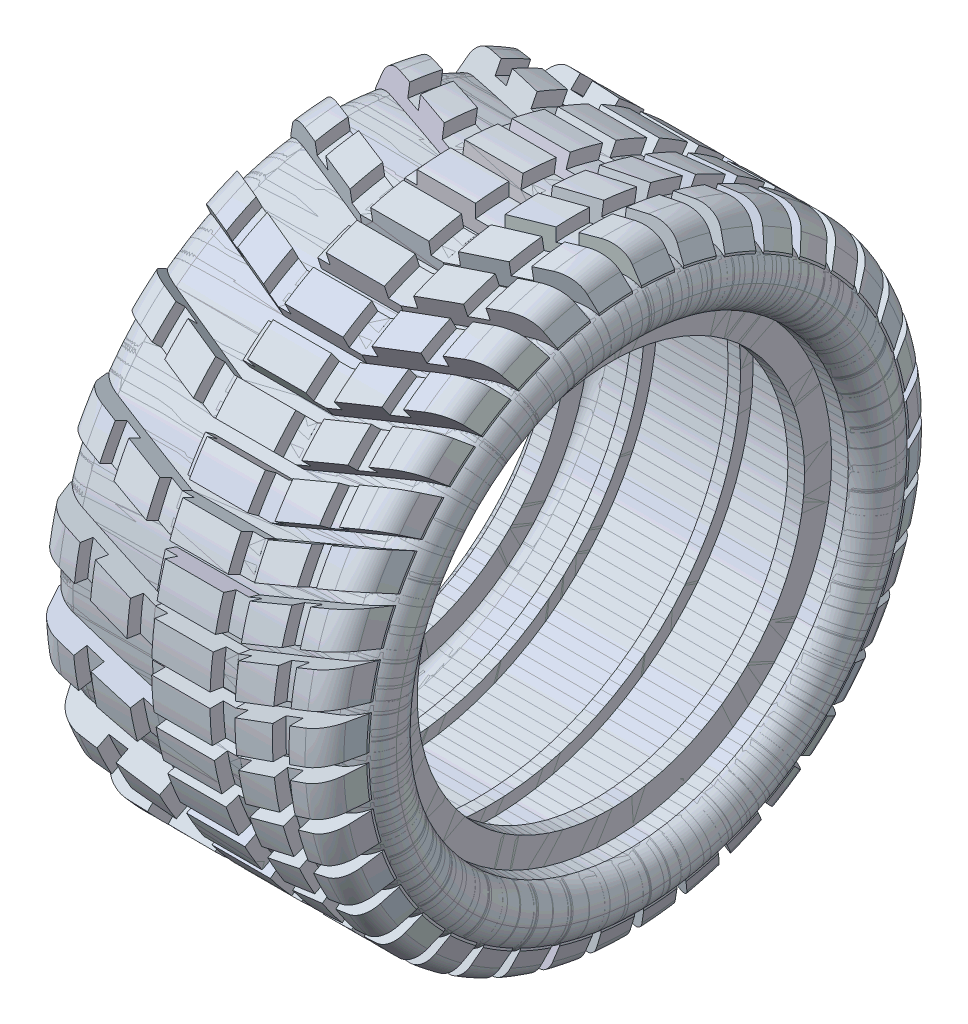
SolidWorks part; units mm, degrees
material "Rubber"
ref_plane "Front Plane" through (0, 0, 0) normal (0, 0, 1) x (1, 0, 0)
ref_plane "Top Plane" through (0, 0, 0) normal (0, 1, 0) x (1, 0, 0)
ref_plane "Right Plane" through (0, 0, 0) normal (1, 0, 0) x (0, 0, -1)
sketch "Sketch1" plane through (0, 0, 0) normal (0, 0, 1) x (1, 0, 0)
  line L0 (-30.5, 25.5) -> (-30.5, -25.5) construction
  line L1 (-30.5, 23.25) -> (-32.5, 23.25) construction
  line L2 (-32.5, -26.5) -> (-32.5, 26.5) construction
  line L3 (-32.5, 26.5) -> (-34.5, 26.5) construction
  line L4 (-30.5, 25.5) -> (-30.5, 23.25)
  line L5 (-30.5, 23.25) -> (-32.5, 23.25)
  line L6 (-32.5, 23.25) -> (-32.5, 26.5)
  line L7 (-32.5, 26.5) -> (-34.5, 26.5)
  line L8 (-17.25, 23.25) -> (-17.25, 39.4881) construction
  line L9 (-5, 23.25) -> (-29.5, 23.25) construction
  line L10 (-33.1867, 33.3757) -> (-1.3133, 33.3757)
  line L11 (-30.5, 25.5) -> (-30.5, 25.9278)
  line L12 (-32.6213, 28.0492) -> (-33.1867, 28.0492)
  line L13 (-33.1867, 31.5757) -> (-29.5, 31.5757)
  line L14 (-16.5, 30.0757) -> (-18, 30.0757)
  line L15 (-18, 30.0757) -> (-18, 31.5757)
  line L16 (-29.5, 31.5757) -> (-29.5, 30.0757)
  line L17 (-29.5, 30.0757) -> (-28, 30.0757)
  line L18 (-28, 30.0757) -> (-28, 31.5757)
  line L19 (-28, 31.5757) -> (-18, 31.5757)
  line L20 (-30.5, 25.9278) -> (-32.6213, 28.0492)
  line L21 (-4, 25.9278) -> (-1.8787, 28.0492)
  line L22 (-6.5, 31.5757) -> (-16.5, 31.5757)
  line L23 (-6.5, 30.0757) -> (-6.5, 31.5757)
  line L24 (-5, 30.0757) -> (-6.5, 30.0757)
  line L25 (-5, 31.5757) -> (-5, 30.0757)
  line L26 (-16.5, 30.0757) -> (-16.5, 31.5757)
  line L27 (-1.3133, 31.5757) -> (-5, 31.5757)
  line L28 (-1.8787, 28.0492) -> (-1.3133, 28.0492)
  line L29 (-4, 25.5) -> (-4, 25.9278)
  line L30 (-2, 26.5) -> (0, 26.5)
  line L31 (-2, 23.25) -> (-2, 26.5)
  line L32 (-4, 23.25) -> (-2, 23.25)
  line L33 (-4, 25.5) -> (-4, 23.25)
  line L34 (0, 0) -> (-51.0167, 0) construction
  line L35 (-36.75, 29.8124) -> (-36.75, 39.4881) construction
  line L36 (2.25, 29.8124) -> (2.25, 36.5986) construction
  arc A0 (-34.5, 26.5) -> (-33.1867, 33.3757) centre (-33.1867, 29.8124) cw
  arc A1 (-33.1867, 28.0492) -> (-33.1867, 31.5757) centre (-33.1867, 29.8124) cw
  arc A2 (-1.3133, 28.0492) -> (-1.3133, 31.5757) centre (-1.3133, 29.8124) ccw
  arc A3 (0, 26.5) -> (-1.3133, 33.3757) centre (-1.3133, 29.8124) ccw
  point P38 (-17.25, 30.0757)
  point P39 (-17.25, 33.3757)
  dimension "D1" = 7
  dimension "D2" = 1.8
  dimension "D3" = 1.5
  dimension "D4" = 10
  dimension "D5" = 45
  dimension "D6" = 3
  dimension "D7" = 39
revolve "Revolve1" add sketch "Sketch1" angle 360 about L34
ref_plane "Plane1" through (0, 50, 0) normal (0, 1, 0) x (-1, 0, 0)
sketch "Sketch3" plane through (0, 50, 0) normal (0, 1, 0) x (-1, 0, 0)
  line L0 (33.1867, 0) -> (1.3133, 0) construction
  line L1 (17.25, 0.5) -> (17.25, -0.5) construction
  line L2 (22.25, -0.5) -> (12.25, -0.5) construction
  line L3 (22.25, -0.5) -> (22.25, -4.5) construction
  line L4 (22.25, -4.5) -> (12.25, -4.5) construction
  line L5 (12.25, -0.5) -> (12.25, -4.5) construction
  line L6 (22.25, 4.5) -> (12.25, 4.5)
  line L7 (22.25, 4.5) -> (22.25, 0.5)
  line L8 (22.25, 0.5) -> (12.25, 0.5)
  line L9 (12.25, 4.5) -> (12.25, 0.5) construction
  line L10 (33.1867, -33.3757) -> (33.1867, 33.3757) construction
  line L11 (-1.25, -0.4136) -> (-1.25, -4.4136)
  line L12 (1.3133, -33.3757) -> (1.3133, 33.3757) construction
  line L13 (35.75, -9.4136) -> (35.75, -5.4136) construction
  line L14 (-1.25, -0.4136) -> (12.25, 4.5)
  line L15 (12.25, 0.5) -> (-1.25, -4.4136)
  line L16 (22.25, -0.5) -> (35.75, -5.4136) construction
  line L17 (22.25, -4.5) -> (35.75, -9.4136) construction
  line L21 (35.75, -29.8124) -> (35.75, 29.8124)
  line L22 (35.75, -29.8124) -> (35.75, 29.8124) construction
  line L24 (-1.25, 29.8124) -> (-1.25, -29.8124)
  line L25 (-1.25, 29.8124) -> (-1.25, -29.8124) construction
  point P12 (17.25, 0)
  dimension "D1" = 4
  dimension "D2" = 10
  dimension "D3" = 1
  dimension "D4" = 200
  dimension "D5" = 200
  dimension "D6" = 1
  dimension "D7" = 1
extrude "Boss-Extrude1" add sketch "Sketch3" against normal up to next
ref_plane "Plane2" through (-17.25, 0, 0) normal (-1, 0, 0) x (0, 0, 1)
pattern_circular "CirPattern1" count 20 over 360 about axis through (0, 0, 0) along (1, 0, 0) of "Boss-Extrude1"
sketch "Sketch4" plane through (0, 0, 0) normal (0, 0, 1) x (1, 0, 0)
  line L0 (-35.95, 32.0622) -> (-34.95, 34.5075)
  line L1 (-22.25, 33.372) -> (-12.25, 33.372) construction
  line L2 (-32.1732, 36.372) -> (-30.25, 36.372)
  line L3 (-1.3133, 0) -> (-33.1867, 0) construction
  line L4 (-33.1867, 31.5757) -> (-33.1867, -31.5757) construction
  line L5 (-17.25, 0) -> (-17.25, 64.8866) construction
  line L6 (-1.3133, 9.8185) -> (-1.3133, 3.4806) construction
  line L7 (-35.95, 32.0622) -> (-43.929, 56.5045)
  line L8 (-43.929, 56.5045) -> (9.429, 56.5045)
  line L9 (-20.75, 36.372) -> (-20.75, 34.772)
  line L10 (-20.75, 34.772) -> (-23.75, 34.772)
  line L11 (-23.75, 34.772) -> (-23.75, 36.372)
  line L12 (-28.25, 36.372) -> (-28.25, 34.772)
  line L13 (-28.25, 34.772) -> (-30.25, 34.772)
  line L14 (-30.25, 34.772) -> (-30.25, 36.372)
  line L15 (-28.25, 36.372) -> (-23.75, 36.372)
  line L16 (-20.75, 36.372) -> (-13.75, 36.372)
  line L17 (-6.25, 36.372) -> (-10.75, 36.372)
  line L18 (-4.25, 34.772) -> (-4.25, 36.372)
  line L19 (-6.25, 34.772) -> (-4.25, 34.772)
  line L20 (-6.25, 36.372) -> (-6.25, 34.772)
  line L21 (-10.75, 34.772) -> (-10.75, 36.372)
  line L22 (-13.75, 34.772) -> (-10.75, 34.772)
  line L23 (-13.75, 36.372) -> (-13.75, 34.772)
  line L24 (1.45, 32.0622) -> (9.429, 56.5045)
  line L25 (-2.3268, 36.372) -> (-4.25, 36.372)
  line L26 (1.45, 32.0622) -> (0.45, 34.5075)
  line L27 (-36.75, 29.8124) -> (-36.75, -29.8124) construction
  arc A0 (-34.95, 34.5075) -> (-32.1732, 36.372) centre (-32.1732, 33.372) cw
  arc A1 (0.45, 34.5075) -> (-2.3268, 36.372) centre (-2.3268, 33.372) ccw
  arc A2 (-33.1867, 33.3757) -> (-36.75, 29.8124) centre (-33.1867, 29.8124) ccw construction
  point P31 (-17.25, 36.372)
  point P39 (-17.25, 56.5045)
  dimension "D1" = 3
  dimension "D2" = 3
  dimension "D3" = 0.8
  dimension "D4" = 7
  dimension "D5" = 3
  dimension "D6" = 2
  dimension "D7" = 22
  dimension "D8" = 1.6
  dimension "D9" = 1
revolve "Cut-Revolve2" cut sketch "Sketch4" angle 360 about L3
move or copy body "Body-Move/Copy1" bodies to move or copy 105 copy yes number of copies 1 rotation origin (0, 0, 0) rotation axis (1, 0, 0) rotation angle 9
mirror "Mirror2" about plane through (-17.25, 0, 0) normal (-1, 0, 0) of bodies 108
combine bodies "Combine1" operation type add bodies to combine 105 109
